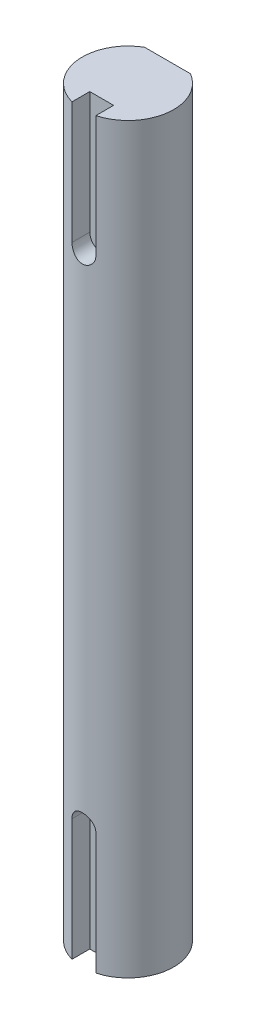
SolidWorks part; units mm, degrees
material "AISI 1045 Steel, cold drawn"
ref_plane "X-Y Datum" through (0, 0, 0) normal (0, 0, 1) x (1, 0, 0)
ref_plane "X-Z Datum" through (0, 0, 0) normal (0, 1, 0) x (1, 0, 0)
ref_plane "Y-Z Datum" through (0, 0, 0) normal (1, 0, 0) x (0, 0, -1)
sketch "Sketch1" plane through (0, 0, 0) normal (0, 1, 0) x (1, 0, 0)
  line L0 (-2.3876, 4.1208) -> (2.3876, 4.1208)
  circle A0 centre (0, 0) radius 4.7625
  dimension "D1" = 9.525
  dimension "D2" = 4.7752
extrude "Boss-Extrude1" add sketch "Sketch1" along normal blind 38.735 and the other way blind 38.735 contours L0 A0 region at (0, 0, 0.1312)
sketch "Sketch2" plane through (0, -38.735, 0) normal (0, -1, 0) x (1, 0, 0)
  line L0 (-1.25, 4.5955) -> (-1.25, 2.7375)
  line L1 (-1.25, 2.7375) -> (1.25, 2.7375)
  line L2 (1.25, 2.7375) -> (1.25, 4.5955)
  arc A0 (2.3876, -4.1208) -> (-2.3876, -4.1208) centre (0, 0) ccw construction
  circle A1 centre (0, 0) radius 4.7625 construction
  point P5 (0, -4.7625)
  point P8 (0, 2.7375)
  dimension "D1" = 2.5
  dimension "D2" = 7.5
extrude "Cut-Extrude1" [suppressed] cut sketch "Sketch2" against normal blind 12.7 and the other way through all
sketch "Sketch3" plane through (0, 38.735, 0) normal (0, 1, 0) x (1, 0, 0)
  line L0 (-1.25, -4.5955) -> (-1.25, -2.7375)
  line L1 (-1.25, -2.7375) -> (1.25, -2.7375)
  line L2 (1.25, -2.7375) -> (1.25, -4.5955)
  circle A0 centre (0, 0) radius 4.7625 construction
  arc A1 (-1.25, -4.5955) -> (1.25, -4.5955) centre (0, 0) ccw
  point P6 (0, -2.7375)
  point P9 (0, 4.7625)
  dimension "D1" = 2.5
  dimension "D2" = 7.5
extrude "Cut-Extrude2" [suppressed] cut sketch "Sketch3" against normal blind 12.7
ref_plane "Plane1" through (0, 0, 2.7432) normal (0, 0, 1) x (1, 0, 0)
sketch "Sketch4" plane through (0, 0, 2.7432) normal (0, 0, 1) x (1, 0, 0)
  line L0 (4.7625, 38.735) -> (-4.7625, 38.735) construction
  line L1 (-1.2446, 38.735) -> (1.2446, 38.735)
  line L2 (-1.2446, 38.735) -> (-1.2446, 26.035)
  line L3 (-1.2446, 26.035) -> (1.2446, 26.035)
  line L4 (1.2446, 38.735) -> (1.2446, 26.035)
  line L5 (-4.7625, -38.735) -> (4.7625, -38.735) construction
  line L6 (-1.2446, -38.735) -> (1.2446, -38.735)
  line L7 (-1.2446, -38.735) -> (-1.2446, -26.035)
  line L8 (-1.2446, -26.035) -> (1.2446, -26.035)
  line L9 (1.2446, -38.735) -> (1.2446, -26.035)
  circle A0 centre (0, 26.035) radius 1.2446
  circle A1 centre (0, -26.035) radius 1.2446
  point P12 (0, -26.035)
  point P13 (0, 26.035)
  dimension "D1" = 2.4892
  dimension "D3" = 12.7
extrude "Cut-Extrude4" cut sketch "Sketch4" along normal through all contours A1 L7 L6 L9 | L8 A1 | A0 L4 L1 L2 | L3 A0 | L3 A0 | A1 region at (0, 32.8705, 2.7432) region at (0, 26.5632, 2.7432) region at (0, 25.5068, 2.7432) region at (0, -32.8705, 2.7432) region at (0, -26.5632, 2.7432)
